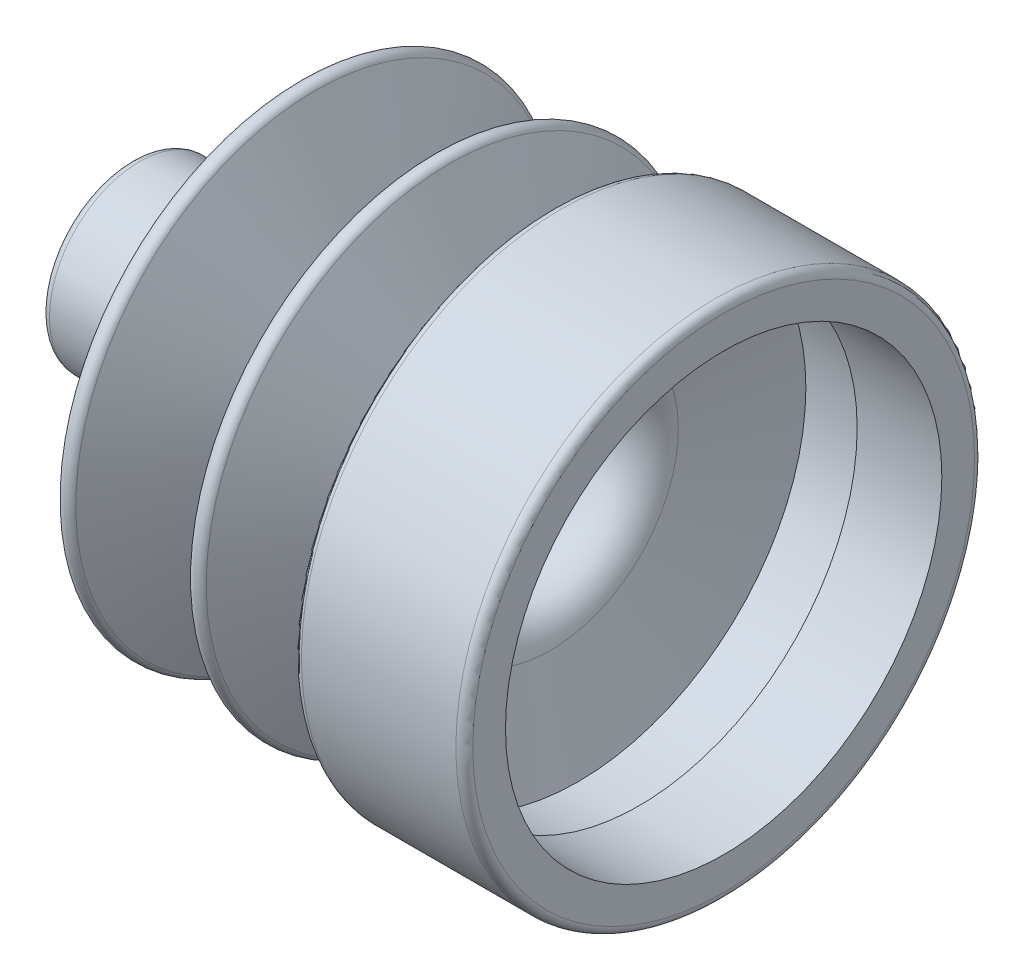
SolidWorks part; units mm, degrees
material "POLYURETHANE (11671)"
ref_plane "Front Plane" through (0, 0, 0) normal (0, 0, 1) x (1, 0, 0)
ref_plane "Top Plane" through (0, 0, 0) normal (0, 1, 0) x (1, 0, 0)
ref_plane "Right Plane" through (0, 0, 0) normal (1, 0, 0) x (0, 0, -1)
sketch "Sketch1" plane through (0, 0, 0) normal (0, 0, 1) x (1, 0, 0)
  line L0 (0, 0) -> (0, 18.8119)
  line L1 (-0.635, 19.4469) -> (-12.2198, 19.4469)
  line L2 (-12.8308, 18.9848) -> (-15.301, 10.2586)
  line L3 (-16.4791, 10.1459) -> (-20.5586, 18.2457)
  line L4 (-21.7067, 18.2164) -> (-25.3685, 9.9194)
  line L5 (-26.5166, 9.8902) -> (-30.5962, 17.9899)
  line L6 (-31.7743, 17.8773) -> (-34.7942, 7.2089)
  line L7 (-35.4052, 6.7469) -> (-43.815, 6.7469)
  line L8 (-44.45, 6.1119) -> (-44.45, 0)
  line L9 (-44.45, 0) -> (0, 0) construction
  line L10 (-12.7, 19.4469) -> (-38.1, 19.4469) construction
  line L11 (0, 0) -> (-44.45, 0)
  arc A0 (0, 18.8119) -> (-0.635, 19.4469) centre (-0.635, 18.8119) ccw
  arc A1 (-12.2198, 19.4469) -> (-12.8308, 18.9848) centre (-12.2198, 18.8119) ccw
  arc A2 (-44.45, 6.1119) -> (-43.815, 6.7469) centre (-43.815, 6.1119) cw
  arc A3 (-35.4052, 6.7469) -> (-34.7942, 7.2089) centre (-35.4052, 7.3819) ccw
  arc A4 (-15.301, 10.2586) -> (-16.4791, 10.1459) centre (-15.9119, 10.4315) cw
  arc A5 (-25.3685, 9.9194) -> (-26.5166, 9.8902) centre (-25.9495, 10.1758) cw
  arc A6 (-20.5586, 18.2457) -> (-21.7067, 18.2164) centre (-21.1258, 17.96) ccw
  arc A7 (-30.5962, 17.9899) -> (-31.7743, 17.8773) centre (-31.1633, 17.7043) ccw
  point P14 (0, 19.4469)
  point P20 (-44.45, 6.7469)
  point P23 (-34.925, 6.7469)
  point P30 (-21.1637, 19.4469)
  point P33 (-31.33, 19.4469)
  dimension "D6" = 0.635
  dimension "D1" = 19.4469
  dimension "D2" = 9.525
  dimension "D3" = 12.7
  dimension "D4" = 44.45
  dimension "D5" = 6.7469
revolve "Revolve1" add sketch "Sketch1" angle 360 about L11
shell "Shell1" thickness 2.3813 removed face at (0, 18.8119, 0)
sketch "Sketch2" plane through (0, 0, 0) normal (0, 0, 1) x (1, 0, 0)
  line L0 (0, -18.8119) -> (0, 18.8119) construction
  line L1 (0, 17.1564) -> (-6.35, 17.1564)
  line L2 (0, 17.1564) -> (0, 16.3626)
  line L3 (0, 16.3626) -> (-6.35, 16.3626)
  line L4 (-6.35, 17.1564) -> (-6.35, 16.3626)
  line L5 (0, -17.0656) -> (0, 17.0656) construction
  dimension "D1" = 6.35
  dimension "D2" = 0.7937
ref_axis "Axis1" through (-56.5582, 0, 0) along (1, 0, 0)
revolve "Revolve2" add sketch "Sketch2" angle 360 about axis through (-56.5582, 0, 0) along (1, 0, 0)
sketch "Sketch3" plane through (-44.45, 0, 0) normal (-1, 0, 0) x (0, 0, 1)
  circle A0 centre (0, 0) radius 3.9688
extrude "Cut-Extrude1" cut sketch "Sketch3" against normal up to next
